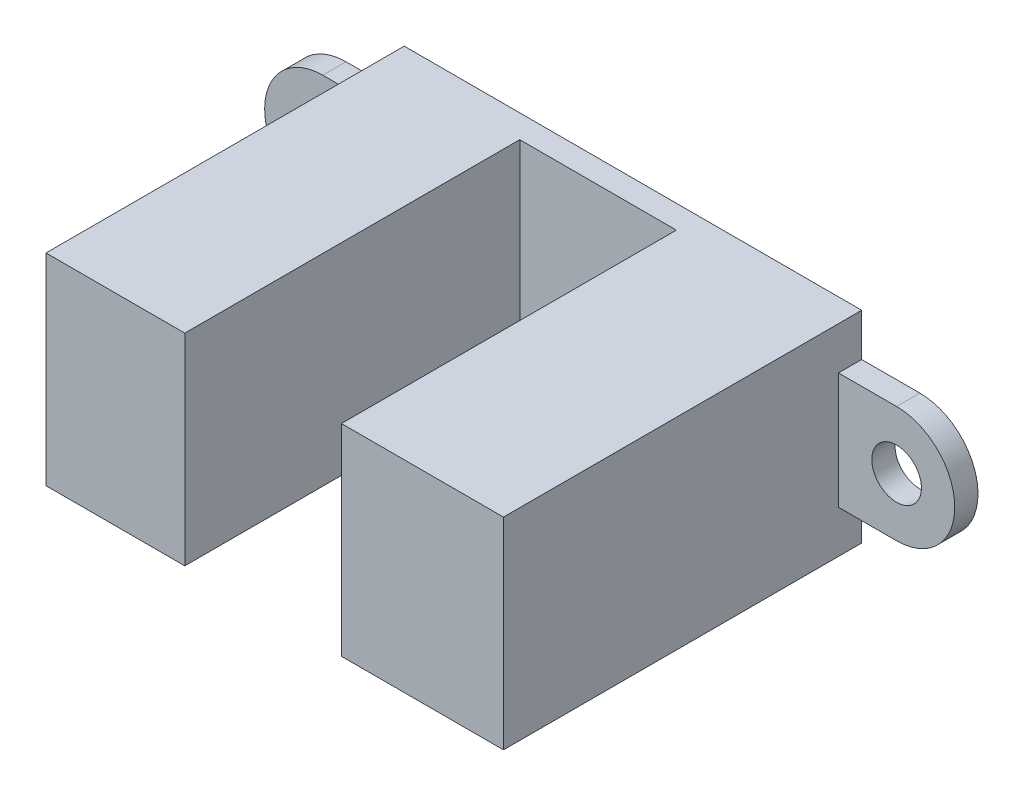
SolidWorks part; units mm, degrees
ref_plane "Front Plane" through (0, 0, 0) normal (0, 0, 1) x (1, 0, 0)
ref_plane "Top Plane" through (0, 0, 0) normal (0, 1, 0) x (1, 0, 0)
ref_plane "Right Plane" through (0, 0, 0) normal (1, 0, 0) x (0, 0, -1)
sketch "Sketch1" plane through (0, 0, 0) normal (0, 0, 1) x (1, 0, 0)
  line L0 (0, 6.5) -> (0, -6.5) construction
  line L1 (-14.75, -6.5) -> (14.75, -6.5)
  line L2 (-14.75, -6.5) -> (-14.75, 6.5)
  line L3 (-14.75, 6.5) -> (14.75, 6.5)
  line L4 (14.75, -6.5) -> (14.75, 6.5)
  line L5 (-14.75, -6.5) -> (14.75, 6.5) construction
  line L6 (-14.75, 6.5) -> (14.75, -6.5) construction
  line L7 (14.75, 3.75) -> (18.5, 3.75)
  line L8 (14.75, 3.75) -> (14.75, -3.75)
  line L9 (14.75, -3.75) -> (18.5, -3.75)
  line L10 (18.5, 3.75) -> (18.5, -3.75)
  line L11 (-14.75, -3.75) -> (-18.5, -3.75)
  line L12 (-18.5, 3.75) -> (-18.5, -3.75)
  line L13 (-14.75, 3.75) -> (-18.5, 3.75)
  line L14 (-14.75, 3.75) -> (-14.75, -3.75)
  circle A0 centre (18.5, 0) radius 3.75
  circle A1 centre (-18.5, 0) radius 3.75
  point P0 (0, 0)
  dimension "D3" = 7.5
  dimension "D1" = 13
  dimension "D2" = 29.5
extrude "Back Plate" add sketch "Sketch1" along normal blind 1.5 contours A1 L12 | L13 A1 L14 | A1 L12 | L2 A1 L11 | L1 L4 L8 L3 L2 L14 | A0 L4 L9 | A0 L7 L8 | L10 A0 | L10 A0 region at (0, 0, 0) region at (-15.5876, -2.9124, 0) region at (15.5876, -2.9124, 0) region at (-15.5876, 2.9124, 0) region at (-16.9085, 0, 0) region at (-20.0915, 0, 0) region at (15.5876, 2.9124, 0) region at (16.9085, 0, 0) region at (20.0915, 0, 0)
sketch "Sketch2" plane through (0, 0, 0) normal (1, 0, 0) x (0, 0, -1)
  line L0 (-1.5, -6.5) -> (0, -6.5) construction
  line L1 (-1.5, 6.5) -> (-23.1, 6.5)
  line L2 (-1.5, 6.5) -> (-1.5, -6.5)
  line L3 (-1.5, -6.5) -> (-23.1, -6.5)
  line L4 (-23.1, 6.5) -> (-23.1, -6.5)
  dimension "D1" = 13
  dimension "D2" = 21.6
extrude "Detector Side" add sketch "Sketch2" against normal blind 10.45 from surface starting at face at (14.75, 5.125, 0.75)
extrude "Emitter Side" add sketch "Sketch2<2>" along normal blind 8.95 from surface starting at face at (-14.75, -5.125, 0.75)
sketch "Sketch2<2>" plane through (0, 0, 0) normal (1, 0, 0) x (0, 0, -1) same geometry as "Sketch2"
hole_wizard "Ø3.2 (3.2) Diameter Hole1" positions "Sketch3" profile "Sketch4" hole size "Ø3.2" standard "ANSI Metric"
sketch "Sketch3" plane through (0, 0, 0) normal (0, 0, -1) x (-1, 0, 0)
  line L0 (-18.5, 3.75) -> (-18.5, -3.75) construction
  line L2 (-22.25, 0) -> (22.25, 0) construction
  line L4 (18.5, 3.75) -> (18.5, -3.75) construction
  arc A0 (-18.5, 3.75) -> (-18.5, -3.75) centre (-18.5, 0) ccw construction
  arc A1 (18.5, -3.75) -> (18.5, 3.75) centre (18.5, 0) ccw construction
  point P0 (-18.5, 0)
  point P2 (18.5, 0)
sketch "Sketch4" plane through (18.5, 0, 0) normal (1, 0, 0) x (0, 1, 0)
  line L0 (0, 0) -> (0, 4.9614)
  line L1 (0, 4.9614) -> (1.6, 4)
  line L2 (1.6, 4) -> (1.6, 0)
  line L5 (1.6, 0) -> (0, 0)
  line L10 (0, 4.9614) -> (-1.6, 4) construction
  line L11 (0, -6.35) -> (0, 107.95) construction
  dimension "Hole Dia." = 3.2
  dimension "Hole Depth" = 4
  dimension "Drill Angle" = 118
